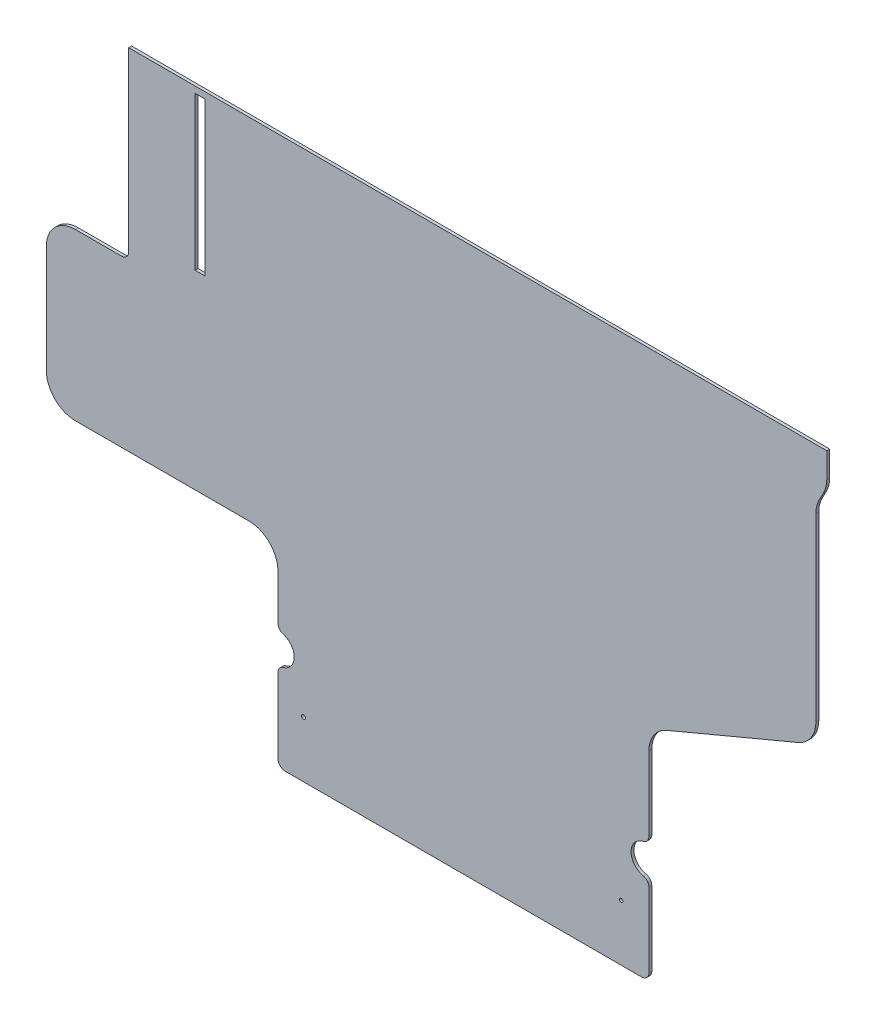
SolidWorks part; units mm, degrees
material "Plastique personnalisé"
ref_plane "Plan de face" through (0, 0, 0) normal (0, 0, 1) x (1, 0, 0)
ref_plane "Plan de dessus" through (0, 0, 0) normal (0, 1, 0) x (1, 0, 0)
ref_plane "Plan de droite" through (0, 0, 0) normal (1, 0, 0) x (0, 0, -1)
sketch "Esquisse1" plane through (0, 0, 0) normal (0, 0, 1) x (1, 0, 0)
  line L0 (40.2651, 230.7932) -> (75.9648, 230.6489) construction
  line L1 (69.0094, 230.5808) -> (69.0094, 229.7222)
  line L2 (68.8912, 229.2505) -> (68.7524, 228.9911)
  line L3 (68.6342, 228.5195) -> (68.6342, 222.2996)
  line L4 (68.0213, 221.3775) -> (63.4923, 219.4763)
  line L5 (62.8794, 218.5542) -> (62.8794, 215.9994)
  line L6 (62.6294, 211.6833) -> (50.3468, 211.6833)
  line L7 (50.0968, 211.9333) -> (50.0968, 214.5061)
  line L8 (49.0968, 218.5268) -> (43.115, 218.5268)
  line L9 (42.115, 219.5268) -> (42.115, 223.2367)
  line L10 (43.115, 224.2367) -> (44.7044, 224.2367)
  line L11 (44.9544, 224.4867) -> (44.9544, 230.5808)
  line L12 (44.9544, 230.5808) -> (69.0094, 230.5808)
  line L13 (62.8794, 214.4881) -> (62.8794, 211.9333)
  line L14 (50.0968, 215.9794) -> (50.0968, 217.5268)
  line L16 (47.2413, 230.3627) -> (47.5783, 230.3627)
  line L17 (47.2413, 230.3627) -> (47.2413, 225.0827)
  line L18 (47.2413, 225.0827) -> (47.5783, 225.0827)
  line L19 (47.5783, 230.3627) -> (47.5783, 225.0827)
  arc A0 (69.0094, 229.7222) -> (68.8912, 229.2505) centre (68.0094, 229.7222) cw
  arc A1 (68.7524, 228.9911) -> (68.6342, 228.5195) centre (69.6342, 228.5195) ccw
  arc A2 (68.6342, 222.2996) -> (68.0213, 221.3775) centre (67.6342, 222.2996) cw
  arc A3 (63.4923, 219.4763) -> (62.8794, 218.5542) centre (63.8794, 218.5542) ccw
  arc A4 (50.0968, 217.5268) -> (49.0968, 218.5268) centre (49.0968, 217.5268) ccw
  arc A5 (42.115, 223.2367) -> (43.115, 224.2367) centre (43.115, 223.2367) cw
  arc A6 (43.115, 218.5268) -> (42.115, 219.5268) centre (43.115, 219.5268) cw
  arc A7 (62.8794, 211.9333) -> (62.6294, 211.6833) centre (62.6294, 211.9333) cw
  arc A8 (50.3468, 211.6833) -> (50.0968, 211.9333) centre (50.3468, 211.9333) cw
  arc A9 (44.7044, 224.2367) -> (44.9544, 224.4867) centre (44.7044, 224.4867) ccw
  arc A10 (50.2798, 215.7386) -> (50.2798, 214.7469) centre (50.1418, 215.2428) cw
  arc A11 (62.6805, 215.7547) -> (62.6805, 214.7328) centre (62.787, 215.2438) ccw
  arc A12 (62.6805, 214.7328) -> (62.8794, 214.4881) centre (62.6294, 214.4881) cw
  arc A13 (62.6805, 215.7547) -> (62.8794, 215.9994) centre (62.6294, 215.9994) ccw
  arc A14 (50.2798, 214.7469) -> (50.0968, 214.5061) centre (50.3468, 214.5061) ccw
  arc A15 (50.2798, 215.7386) -> (50.0968, 215.9794) centre (50.3468, 215.9794) cw
  circle A16 centre (50.9772, 213.6184) radius 0.069
  circle A17 centre (61.9246, 213.6184) radius 0.0615
  point P42 (62.8794, 214.7301)
  point P49 (50.0968, 215.7555)
  dimension "D2" = 1
  dimension "D3" = 0.25
  dimension "D4" = 0.25
  dimension "D1" = 35.7
extrude "Boss.-Extru.1" add sketch "Esquisse1" along normal blind 0.1
ref_axis "charniere" through (78.9904, 230.5808, 0.1) along (-1, 0, 0)
sketch "Esquisse2" plane through (0, 0, 0.1) normal (0, 0, 1) x (1, 0, 0)
  line L0 (47.5783, 227.7227) -> (68.6342, 227.7227) construction
  line L1 (47.5783, 225.0827) -> (47.5783, 230.3627) construction
  line L2 (68.6342, 222.2996) -> (68.6342, 228.5195) construction
  line L3 (68.6342, 227.7227) -> (58.1063, 227.7227) construction
  line L4 (58.1063, 227.7227) -> (58.1063, 235.0881) construction
ref_axis "centragenappe" through (58.1063, 227.7227, 0.1) along (0, 1, 0)
